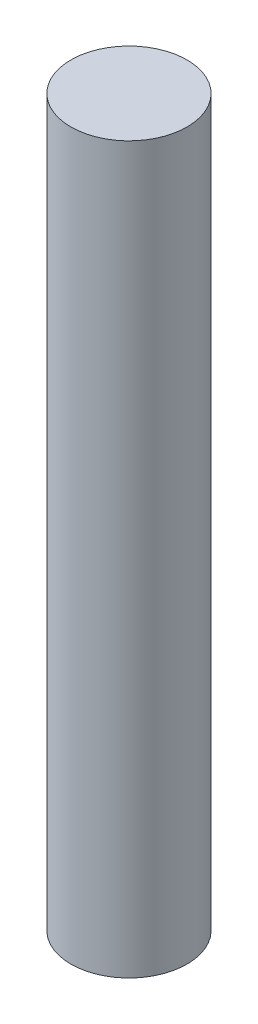
SolidWorks part; units mm, degrees
ref_plane "Front Plane" through (0, 0, 0) normal (0, 0, 1) x (1, 0, 0)
ref_plane "Top Plane" through (0, 0, 0) normal (0, 1, 0) x (1, 0, 0)
ref_plane "Right Plane" through (0, 0, 0) normal (1, 0, 0) x (0, 0, -1)
sketch "Sketch1" plane through (0, 0, 0) normal (0, 1, 0) x (1, 0, 0)
  circle A0 centre (0, 0) radius 3.175
  dimension "D1" = 6.35
extrude "Boss-Extrude1" add sketch "Sketch1" along normal blind 39.624
